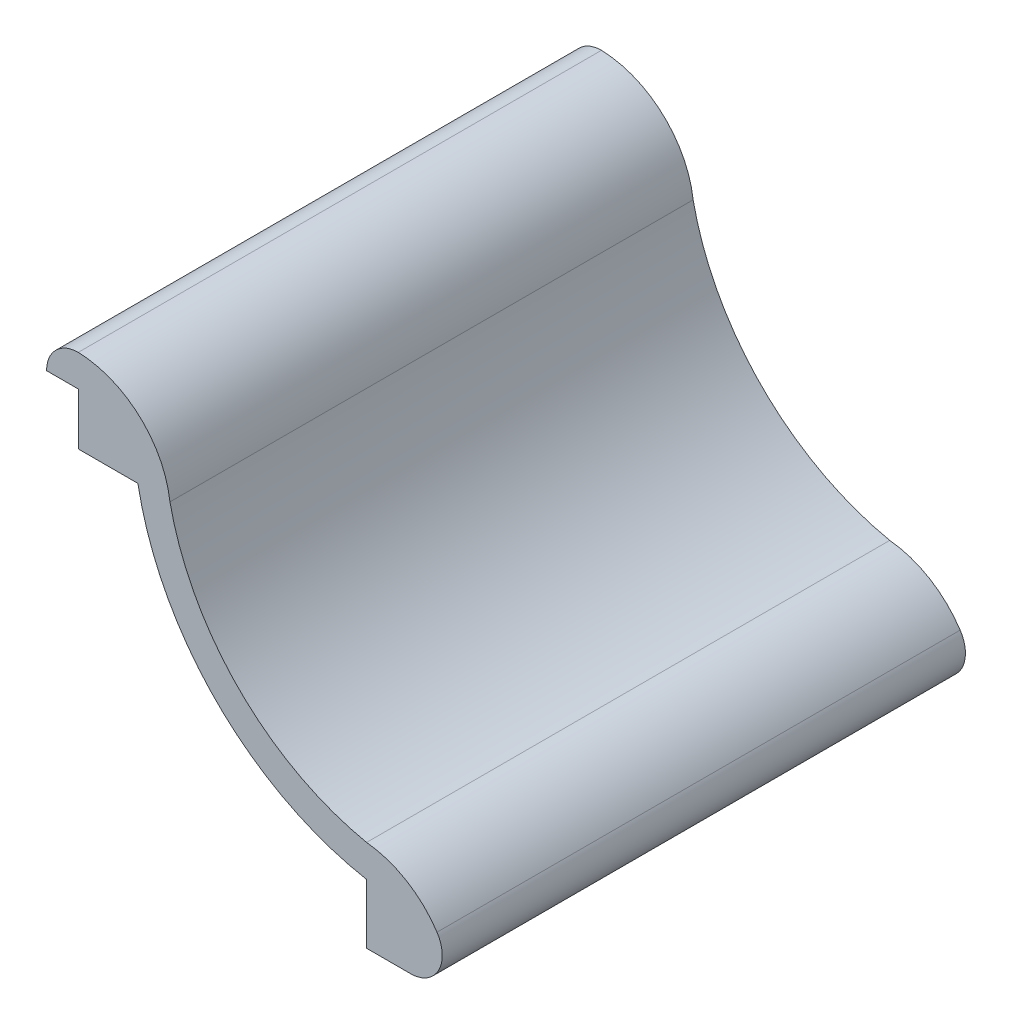
SolidWorks part; units mm, degrees
ref_plane "Front Plane" through (0, 0, 0) normal (0, 0, 1) x (1, 0, 0)
ref_plane "Top Plane" through (0, 0, 0) normal (0, 1, 0) x (1, 0, 0)
ref_plane "Right Plane" through (0, 0, 0) normal (1, 0, 0) x (0, 0, -1)
sketch "Sketch1" plane through (0, 0, 0) normal (0, 0, 1) x (1, 0, 0)
  line L4 (-45.7962, 45.7962) -> (0, 45.7962) construction
  line L6 (0, 45.7962) -> (0, 0) construction
  line L7 (-58.2422, 56.2102) -> (-58.2422, 62.5602)
  line L8 (10.922, -12.446) -> (17.272, -12.446)
  line L9 (-58.2422, 56.2102) -> (-58.2422, 45.7962) construction
  line L10 (-58.2422, 45.7962) -> (-45.7962, 45.7962) construction
  line L11 (0, 0) -> (0, -12.446) construction
  line L12 (0, -12.446) -> (10.922, -12.446) construction
  arc A6 (0, 0) -> (-45.7962, 45.7962) centre (10.3996, 56.1958) cw
  arc A7 (-45.7962, 45.7962) -> (-58.2422, 56.2102) centre (-58.3145, 43.4796) ccw
  arc A8 (0, 0) -> (10.922, -12.446) centre (-1.8079, -12.6018) cw
  arc A9 (-58.2422, 62.5602) -> (-39.3749, 45.7962) centre (-58.3145, 43.4796) cw
  arc A10 (-39.3749, 45.7962) -> (0, 6.4213) centre (10.3996, 56.1958) ccw
  arc A11 (0, 6.4213) -> (17.272, -12.446) centre (-1.8793, -12.6385) cw
  dimension "D1" = 45.7962
  dimension "D2" = 57.15
  dimension "D3" = 10.414
  dimension "D5" = 12.446
  dimension "D4" = 6.35
  dimension "D6" = 12.446
  dimension "D7" = 10.922
extrude "Boss-Extrude1" add sketch "Sketch1" along normal mid plane 209.55 contours L4 | A11 L8 A8 A6 A7 L7 A9 A10 region at (-42.5855, 44.9377, 0)
sketch "Sketch2" plane through (0, 0, 0) normal (0, 0, 1) x (1, 0, 0)
  line L0 (-58.2422, 56.2102) -> (-58.2422, 45.7962)
  line L1 (-58.2422, 45.7962) -> (-45.7962, 45.7962)
  line L2 (0, 0) -> (0, -12.446)
  line L3 (0, -12.446) -> (10.922, -12.446)
  arc A0 (-45.7962, 45.7962) -> (-58.2422, 56.2102) centre (-58.3145, 43.4796) ccw construction
  arc A1 (-45.7962, 45.7962) -> (0, 0) centre (10.3996, 56.1958) ccw construction
  arc A2 (-58.2422, 56.2102) -> (-45.7962, 45.7962) centre (-58.3145, 43.4796) cw
  arc A3 (0, 0) -> (10.922, -12.446) centre (-1.8079, -12.6018) cw
extrude "Boss-Extrude2" add sketch "Sketch2" along normal mid plane 185.1914
sketch "Sketch3" plane through (0, 0, -104.775) normal (0, 0, -1) x (-1, 0, 0)
  line L0 (58.2422, 56.2102) -> (58.2422, 45.7962)
  line L1 (58.2422, 45.7962) -> (45.7962, 45.7962)
  line L2 (0, 0) -> (0, -12.446)
  line L3 (0, -12.446) -> (-10.922, -12.446)
  arc A0 (-10.922, -12.446) -> (0, 0) centre (1.8079, -12.6018) cw
  arc A1 (45.7962, 45.7962) -> (58.2422, 56.2102) centre (58.3145, 43.4796) cw
extrude "Boss-Extrude3" add sketch "Sketch3" against normal offset from surface (5.8293 mm away) 6.35 up to face at (-53.4687, 50.0142, -92.5957)
sketch "Sketch4" plane through (0, 0, 104.775) normal (0, 0, 1) x (1, 0, 0)
  line L0 (-58.2422, 56.2102) -> (-58.2422, 45.7962)
  line L1 (-58.2422, 45.7962) -> (-45.7962, 45.7962)
  line L2 (0, 0) -> (0, -12.446)
  line L3 (0, -12.446) -> (10.922, -12.446)
  arc A0 (-58.2422, 56.2102) -> (-45.7962, 45.7962) centre (-58.3145, 43.4796) cw
  arc A1 (0, 0) -> (10.922, -12.446) centre (-1.8079, -12.6018) cw
extrude "Boss-Extrude4" add sketch "Sketch4" against normal blind 6.35
sketch "Sketch5" plane through (0, 0, 104.775) normal (0, 0, 1) x (1, 0, 0)
  line L0 (-58.2422, 45.7962) -> (-58.2422, 62.5602) construction
  line L2 (-57.7342, 44.7636) -> (-65.5217, 44.7636)
  line L3 (-57.7342, 44.7636) -> (-57.7342, 64.5974)
  line L4 (-57.7342, 64.5974) -> (-65.5217, 64.5974)
  line L5 (-65.5217, 44.7636) -> (-65.5217, 64.5974)
  line L6 (-3.152, -11.938) -> (19.6021, -11.938)
  line L7 (-3.152, -11.938) -> (-3.152, -15.345)
  line L8 (-3.152, -15.345) -> (19.6021, -15.345)
  line L9 (19.6021, -11.938) -> (19.6021, -15.345)
  line L10 (0, -12.446) -> (17.272, -12.446) construction
  dimension "D1" = 0.508
  dimension "D2" = 0.508
extrude "Cut-Extrude1" cut sketch "Sketch5" against normal through all
ref_plane "Plane1" [suppressed] through (-5.969, -5.969, 0) normal (-0.7071, -0.7071, 0) x (-0.7071, 0.7071, 0)
sketch "Sketch6" [suppressed] plane through (-5.969, -5.969, 0) normal (-0.7071, -0.7071, 0) x (-0.7071, 0.7071, 0)
  line L0 (0, 75.9801) -> (64.7656, 75.9801) construction
  line L1 (0, -92.5957) -> (0, 92.5957) construction
  line L2 (64.7656, -92.5957) -> (64.7656, 92.5957) construction
  circle A0 centre (32.3828, 75.9801) radius 6.35
  point P9 (32.3828, 75.9801)
  dimension "D1" = 12.7
extrude "Cut-Extrude2" [suppressed] cut sketch "Sketch6" against normal mid plane 12.7
sketch "Sketch7" plane through (0, 0, 104.775) normal (0, 0, 1) x (1, 0, 0)
  line L5 (-67.6333, 74.6841) -> (21.8261, 74.6841)
  line L6 (-67.6333, 74.6841) -> (-67.6333, -18.424)
  line L7 (-67.6333, -18.424) -> (21.8261, -18.424)
  line L8 (21.8261, 74.6841) -> (21.8261, -18.424)
extrude "Cut-Extrude3" cut sketch "Sketch7" against normal blind 104.775
sketch "Sketch8" plane through (-57.7342, 0, 0) normal (-1, 0, 0) x (0, 0, 1)
  line L0 (0, 62.5515) -> (0, 45.7962) construction
  line L1 (-104.775, 62.5515) -> (0, 62.5515)
  line L2 (-104.775, 62.5515) -> (-104.775, 56.1972)
  line L3 (-104.775, 56.1972) -> (0, 56.1972)
  line L4 (0, 62.5515) -> (0, 56.1972)
  line L5 (-98.9457, 56.1972) -> (-92.5957, 56.1972) construction
extrude "Boss-Extrude5" add sketch "Sketch8" along normal blind 6.35
fillet "Fillet1" radius 6.35 2 edges at (17.2602, -11.938, -52.3875) (-64.0842, 62.5515, -52.3875)
